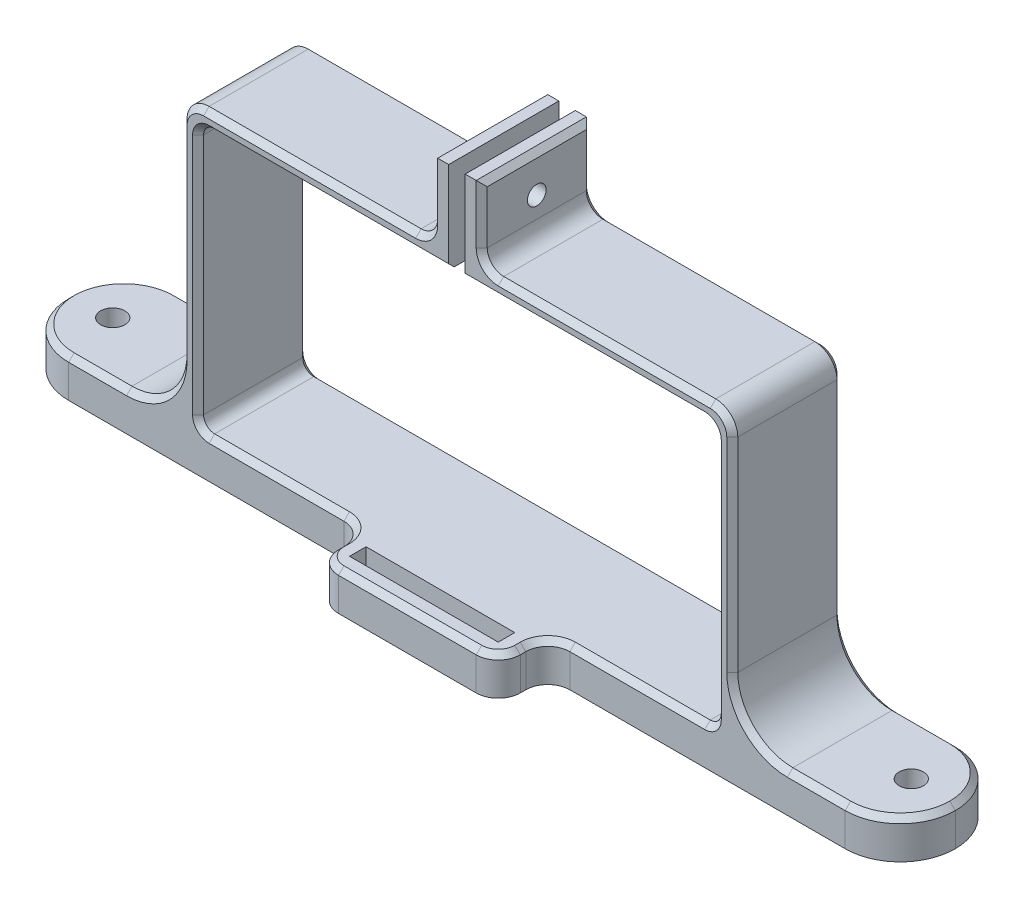
SolidWorks part; units mm, degrees
ref_plane "Front Plane" through (0, 0, 0) normal (0, 0, 1) x (1, 0, 0)
ref_plane "Top Plane" through (0, 0, 0) normal (0, 1, 0) x (1, 0, 0)
ref_plane "Right Plane" through (0, 0, 0) normal (1, 0, 0) x (0, 0, -1)
sketch "Sketch1" plane through (0, 0, 0) normal (0, 1, 0) x (1, 0, 0)
  line L0 (-72.5, 0) -> (-80.5, 0) construction
  line L1 (-80.5, -10) -> (80.5, -10)
  line L2 (-80.5, -10) -> (-80.5, 10)
  line L3 (-80.5, 10) -> (80.5, 10)
  line L4 (80.5, -10) -> (80.5, 10)
  line L5 (-80.5, -10) -> (80.5, 10) construction
  line L6 (-80.5, 10) -> (80.5, -10) construction
  line L7 (72.5, 0) -> (80.5, 0) construction
  circle A0 centre (-72.5, 0) radius 2.2
  circle A1 centre (72.5, 0) radius 2.2
  point P0 (0, 0)
  dimension "D3" = 4.4
  dimension "D1" = 8
  dimension "D2" = 20
  dimension "D4" = 145
extrude "Boss-Extrude1" add sketch "Sketch1" along normal blind 7
sketch "Sketch2" plane through (0, 0, 10) normal (0, 0, 1) x (1, 0, 0)
  line L0 (-80.5, 7) -> (80.5, 7) construction
  line L1 (-50, 7) -> (-47, 7)
  line L2 (-50, 7) -> (-50, 58)
  line L4 (-47, 7) -> (-47, 55)
  line L5 (-1.5, 71.6) -> (1.5, 71.6) construction
  line L6 (-50, 58) -> (-4.5, 58)
  line L8 (-47, 55) -> (-1.5, 55)
  line L12 (-1.5, 71.6) -> (-4.5, 71.6)
  line L13 (-4.5, 58) -> (-4.5, 71.6)
  line L14 (0, 0) -> (0, 117.3961) construction
  line L15 (-1.5, 71.6) -> (-1.5, 55)
  line L16 (1.5, 71.6) -> (1.5, 55)
  line L17 (1.5, 71.6) -> (4.5, 71.6)
  line L18 (4.5, 58) -> (4.5, 71.6)
  line L19 (47, 55) -> (1.5, 55)
  line L20 (50, 58) -> (4.5, 58)
  line L21 (50, 7) -> (50, 58)
  line L22 (47, 7) -> (47, 55)
  point P16 (0, 71.6)
  line M14 (80.5, 7) -> (-80.5, 7)
  dimension "D1" = 3
  dimension "D2" = 3
  dimension "D4" = 48
  dimension "D6" = 1.5
  dimension "D7" = 13.6
  dimension "D5" = 47
  dimension "D3" = 3
extrude "Boss-Extrude2" add sketch "Sketch2" against normal up to surface (20 mm away) contours L22 L21 L20 L18 L17 L16 L19 M14 | L15 L12 L13 L6 L2 L4 L8 M14 region at (-49.1922, 32.5, 10) region at (47.8078, 31, 10) up to face at (0, 3.5, -10)
sketch "Sketch4" plane through (0, 0, 0) normal (0, 1, 0) x (1, 0, 0)
  line L0 (-50, -10) -> (-4.5, -10) construction
  line L1 (-16.5, -10) -> (16.5, -10)
  line L2 (-16.5, -10) -> (-16.5, -19)
  line L3 (-16.5, -19) -> (16.5, -19)
  line L4 (16.5, -10) -> (16.5, -19)
  line L5 (-13.5, -14.5) -> (-16.5, -14.5) construction
  line L6 (-13.5, -13) -> (13.5, -13)
  line L7 (-13.5, -13) -> (-13.5, -16)
  line L8 (-13.5, -16) -> (13.5, -16)
  line L9 (13.5, -13) -> (13.5, -16)
  line L10 (13.5, -14.5) -> (16.5, -14.5) construction
  point P6 (0, -19)
  point P12 (0, -13)
  dimension "D1" = 3
  dimension "D2" = 3
  dimension "D3" = 27
  dimension "D4" = 3
extrude "Boss-Extrude3" add sketch "Sketch4" along normal up to surface (7 mm away) up to face at (0, 7, 0)
sketch "Sketch5" plane through (-4.5, 0, 0) normal (-1, 0, 0) x (0, 0, 1)
  line L0 (-10, 71.6) -> (10, 71.6) construction
  line L1 (10, 58) -> (10, 71.6) construction
  circle A0 centre (0, 64.8) radius 1.7
  point P5 (0, 71.6)
  point P8 (10, 64.8)
  dimension "D1" = 3.4
extrude "Cut-Extrude1" cut sketch "Sketch5" against normal through all
fillet "Fillet1" radius 2 4 edges at (47, 7, 0) (-47, 7, 0) (47, 55, 0) (-47, 55, 0)
fillet "Fillet2" radius 10 6 edges at (80.5, 3.5, 10) (80.5, 3.5, -10) (-80.5, 3.5, -10) (-80.5, 3.5, 10) (50, 7, 0) (-50, 7, 0)
fillet "Fillet3" radius 3 2 edges at (4.5, 58, 0) (-4.5, 58, 0)
fillet "Fillet4" radius 4 4 edges at (-16.5, 3.5, 19) (-16.5, 3.5, 10) (16.5, 3.5, 19) (16.5, 3.5, 10)
fillet "Fillet5" radius 4 2 edges at (50, 58, 0) (-50, 58, 0)
chamfer "Chamfer1" distance 1 angle 45 45 edges at (23.25, 55, -10) (-23.25, 55, -10) (46.4142, 54.4142, -10) (-46.4142, 54.4142, -10) (47, 31, -10) (-47, 31, -10) (46.4142, 7.5858, -10) (-46.4142, 7.5858, -10) (0, 7, -10) (17.6716, 7, 11.1716) (16.5, 7, 14.5) (15.3284, 7, 17.8284) (-23.25, 55, 10) (0, 7, 19) (-46.4142, 54.4142, 10) (-15.3284, 7, 17.8284) (-47, 31, 10) (-16.5, 7, 14.5) (-46.4142, 7.5858, 10) (-17.6716, 7, 11.1716) (-32.75, 7, 10) (-4.5, 71.6, 0) (4.5, 71.6, 0) (52.9289, 9.9289, 10) (50, 35.5, 10) (4.5, 66.3, 10) (48.8284, 56.8284, 10) (5.3787, 58.8787, 10) (26.75, 58, 10) (-4.5, 66.3, -10) (-5.3787, 58.8787, -10) (-26.75, 58, -10) (-48.8284, 56.8284, -10) (-50, 35.5, -10) (-52.9289, 9.9289, -10) (-65.25, 7, -10) (-77.5711, 7, -7.0711) (-77.5711, 7, 7.0711) (-65.25, 7, 10) (-52.9289, 9.9289, 10) (-50, 35.5, 10) (-4.5, 66.3, 10) (-48.8284, 56.8284, 10) (-5.3787, 58.8787, 10) (-26.75, 58, 10)
equation "\"D3@Sketch2\"=\"D2@Sketch2\""
equation "\"D2@Sketch4\"=\"D1@Sketch4\""
